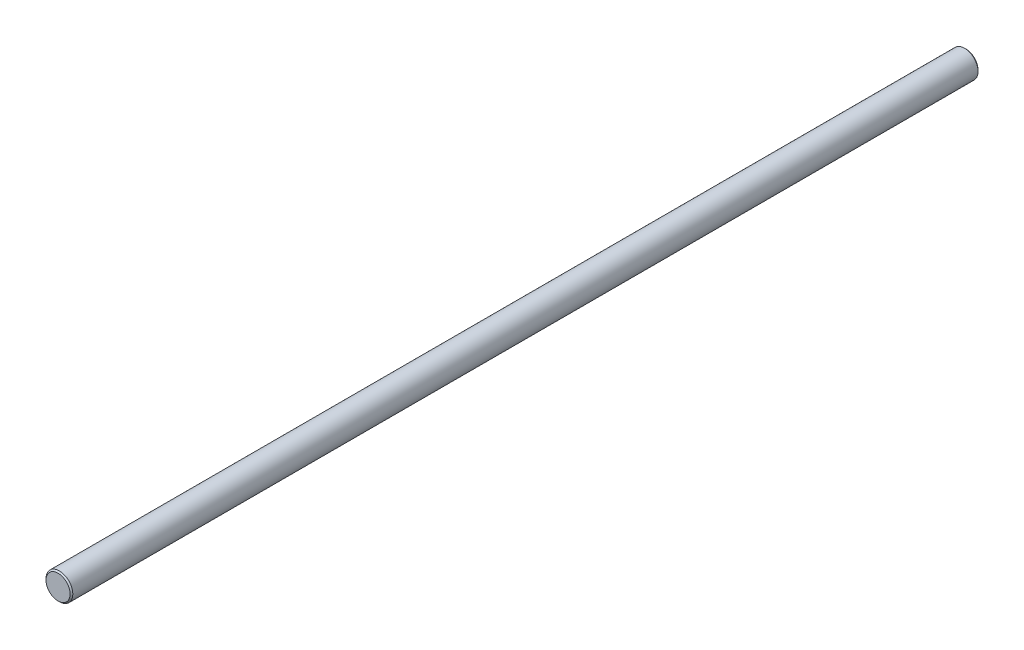
SolidWorks part; units mm, degrees
ref_plane "Front Plane" through (0, 0, 0) normal (0, 0, 1) x (1, 0, 0)
ref_plane "Top Plane" through (0, 0, 0) normal (0, 1, 0) x (1, 0, 0)
ref_plane "Right Plane" through (0, 0, 0) normal (1, 0, 0) x (0, 0, -1)
ref_plane "Plane1" through (0, 0, 339) normal (0, 0, 1) x (1, 0, 0)
sketch "Sketch1" plane through (0, 0, 339) normal (0, 0, 1) x (1, 0, 0)
  circle A0 centre (0, 0) radius 5
extrude "Boss-Extrude1" add sketch "Sketch1" against normal blind 339
chamfer "Chamfer1" distance 0.5 angle 45 2 edges at (-5, 0, 0) (-5, 0, 339)
ref_axis "Axis1" through (0, 0, -4.592) along (0, 0, 1)
